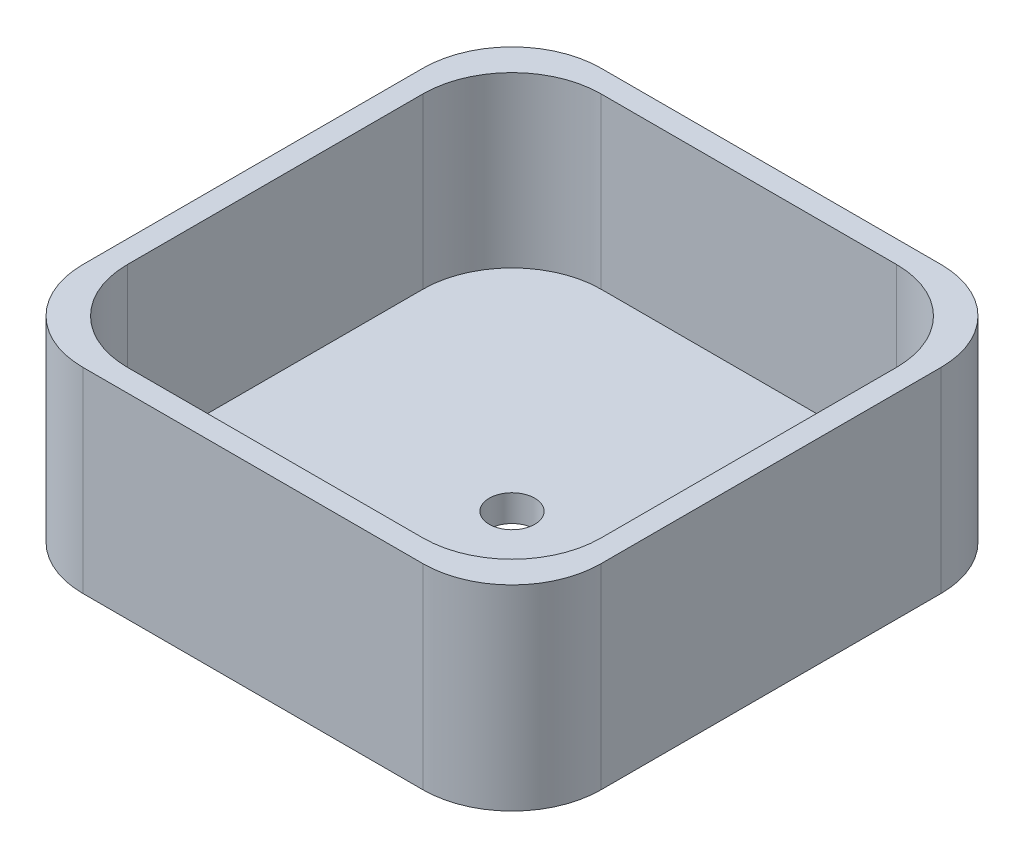
SolidWorks part; units mm, degrees
ref_plane "前视基准面" through (0, 0, 0) normal (0, 0, 1) x (1, 0, 0)
ref_plane "上视基准面" through (0, 0, 0) normal (0, 1, 0) x (1, 0, 0)
ref_plane "右视基准面" through (0, 0, 0) normal (1, 0, 0) x (0, 0, -1)
sketch "草图1" plane through (0, 0, 0) normal (0, 1, 0) x (1, 0, 0)
  line L0 (-29.1, 29.1) -> (29.1, 29.1)
  line L1 (-26.6, -26.6) -> (26.6, -26.6)
  line L2 (-26.6, -26.6) -> (-26.6, 26.6)
  line L3 (-26.6, 26.6) -> (26.6, 26.6)
  line L4 (26.6, -26.6) -> (26.6, 26.6)
  line L5 (-26.6, -26.6) -> (26.6, 26.6) construction
  line L6 (-26.6, 26.6) -> (26.6, -26.6) construction
  line L7 (29.1, -29.1) -> (29.1, 29.1)
  line L8 (-29.1, -29.1) -> (29.1, -29.1)
  line L9 (-29.1, -29.1) -> (-29.1, 29.1)
  circle A0 centre (0, 0) radius 2.55
  point P0 (0, 0)
  dimension "D2" = 5.1
  dimension "D1" = 53.2
  dimension "D3" = 2.5
extrude "凸台-拉伸1" add sketch "草图1" along normal blind 22 contours L0 L7 L8 L9 | L2 L1 L4 L3
extrude "凸台-拉伸2" add sketch "草图1<3>" along normal blind 3 contours L1 L4 L3 L2 A0 region at (-25.8476, 0, 0)
sketch "草图1<3>" plane through (0, 0, 0) normal (0, 1, 0) x (1, 0, 0) same geometry as "草图1"
fillet "圆角1" radius 10 8 edges at (29.1, 11, 29.1) (26.6, 12.5, 26.6) (-26.6, 12.5, 26.6) (26.6, 12.5, -26.6) (-26.6, 12.5, -26.6) (29.1, 11, -29.1) (-29.1, 11, -29.1) (-29.1, 11, 29.1)
